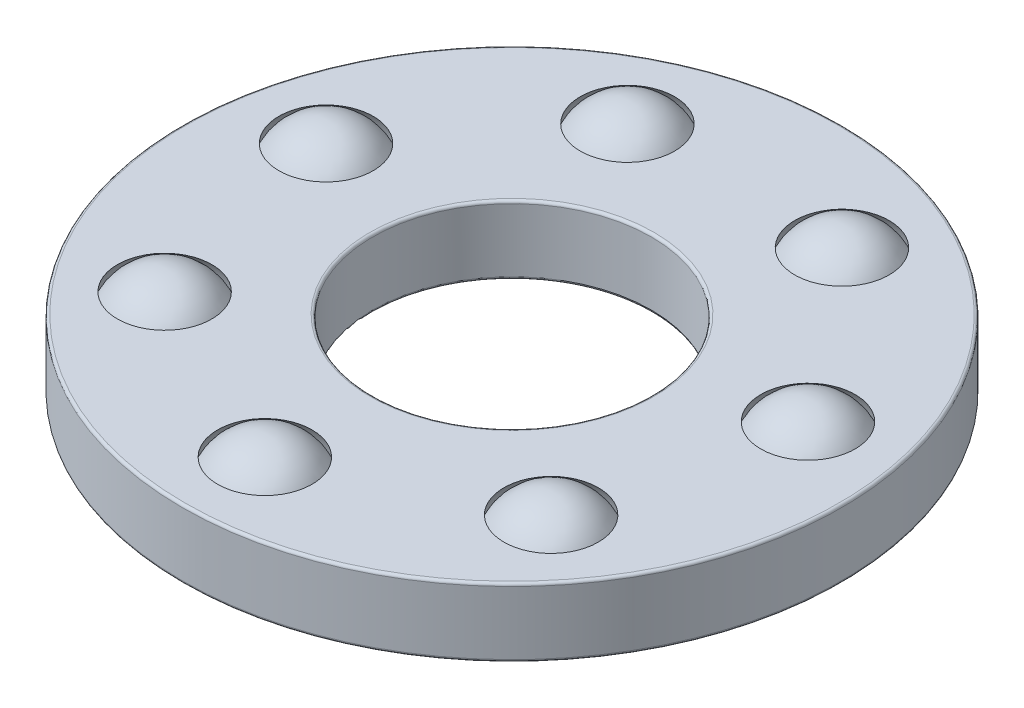
SolidWorks part; units mm, degrees
ref_plane "Front Plane" through (0, 0, 0) normal (0, 0, 1) x (1, 0, 0)
ref_plane "Top Plane" through (0, 0, 0) normal (0, 1, 0) x (1, 0, 0)
ref_plane "Right Plane" through (0, 0, 0) normal (1, 0, 0) x (0, 0, -1)
sketch "Sketch1" plane through (0, 0, 0) normal (1, 0, 0) x (0, 0, -1)
  line L0 (-6, 0) -> (6, 0) construction
  line L1 (0, -2.46) -> (0, 2.46) construction
  line L2 (-6, 0.625) -> (-2.538, 0.625)
  line L3 (-6, 0.625) -> (-6, -0.625)
  line L4 (-6, -0.625) -> (-2.538, -0.625)
  line L5 (-2.538, 0.625) -> (-2.538, -0.625)
  line L6 (-4.5, 1) -> (-4.5, -1) construction
  circle A0 centre (-4.5, 0) radius 1 construction
  dimension "D2" = 1.25
revolve "Revolve1" add sketch "Sketch1" angle 360 about L1
sketch "Sketch3" plane through (0, 0, 0) normal (1, 0, 0) x (0, 0, -1)
  line L0 (-4.5, 1.0625) -> (-4.5, -1.0625)
  line L1 (-4.5, 1) -> (-4.5, -1) construction
  line L2 (-4.4375, 1.0607) -> (-4.4375, -1.0607) construction
  arc A0 (-4.5, 1) -> (-4.5, -1) centre (-4.5, 0) ccw construction
  circle A1 centre (-4.5, 0) radius 1 construction
  arc A2 (-4.5, 1.0625) -> (-4.5, -1.0625) centre (-4.5, 0) ccw
  arc A3 (-4.4375, 1.0607) -> (-4.4375, -1.0607) centre (-4.5, 0) ccw construction
  dimension "D1" = 0.0625
revolve "Cut-Revolve1" cut sketch "Sketch3" angle 360 about L0
sketch "Sketch2" plane through (0, 0, 0) normal (1, 0, 0) x (0, 0, -1)
  line L0 (-4.5, 1) -> (-4.5, -1)
  arc A0 (-4.5, 1) -> (-4.5, -1) centre (-4.5, 0) ccw
  circle A2 centre (-4.5, 0) radius 1 construction
revolve "Revolve2" add sketch "Sketch2" angle 360 about L0
ref_axis "Axis1" through (0, 2.46, 0) along (0, -1, 0)
pattern_circular "CirPattern1" count 7 every 51.429 about axis through (0, 2.46, 0) along (0, -1, 0) of bodies 187
pattern_circular "CirPattern2" count 7 every 51.429 about axis through (0, 2.46, 0) along (0, -1, 0) of "Cut-Revolve1"
sketch "Sketch4" plane through (0, 0, 0) normal (1, 0, 0) x (0, 0, -1)
  line L0 (-6, 0.625) -> (-6, -0.625) construction
  line L1 (-6, 1) -> (-2.538, 1)
  line L2 (-6, 1) -> (-6, 2.46)
  line L3 (-6, 2.46) -> (-2.538, 2.46)
  line L4 (-2.538, 1) -> (-2.538, 2.46)
  line L5 (-6, -2.46) -> (-2.538, -2.46)
  line L6 (-6, -2.46) -> (-6, -1)
  line L7 (-6, -1) -> (-2.538, -1)
  line L8 (-2.538, -2.46) -> (-2.538, -1)
  line L10 (-2.538, 0.625) -> (-2.538, -0.625) construction
  line L11 (0, 0) -> (-6, 0) construction
  line L12 (-6, 0) -> (6, 0) construction
  dimension "Ht" = 4.92
  dimension "Washer Thickness" = 1.46
revolve "Revolve3" add sketch "Sketch4" angle 360 about L1
fillet "Fillet1" radius 0.0492 4 edges at (0, 1, -2.538) (0, 2.46, -2.538) (0, 1, -6) (0, 2.46, -6)
fillet "Fillet2" radius 0.0492 4 edges at (0, -0.625, -2.538) (0, 0.625, -2.538) (0, -0.625, -6) (0, 0.625, -6)
fillet "Fillet3" radius 0.0492 4 edges at (0, -2.46, -2.538) (0, -1, -2.538) (0, -2.46, -6) (0, -1, -6)
delete or keep bodies "Body-Delete/Keep 1" type delete bodies bodies 211 210
equation "\"D2@Sketch1\" = \"Roller Ball Dia@Sketch1\"*.625"
equation "\"Angle@CirPattern1\" = 360/\"Balls@CirPattern1\""
equation "\"D1@CirPattern2\" = \"Balls@CirPattern1\""
equation "\"D2@CirPattern2\" = \"Angle@CirPattern1\""
equation "\"D1@Fillet1\" = \"Th@Sketch1\"*.01"
equation "\"D1@Fillet2\" = \"D1@Fillet1\""
equation "\"D1@Fillet3\" = \"D1@Fillet1\""
